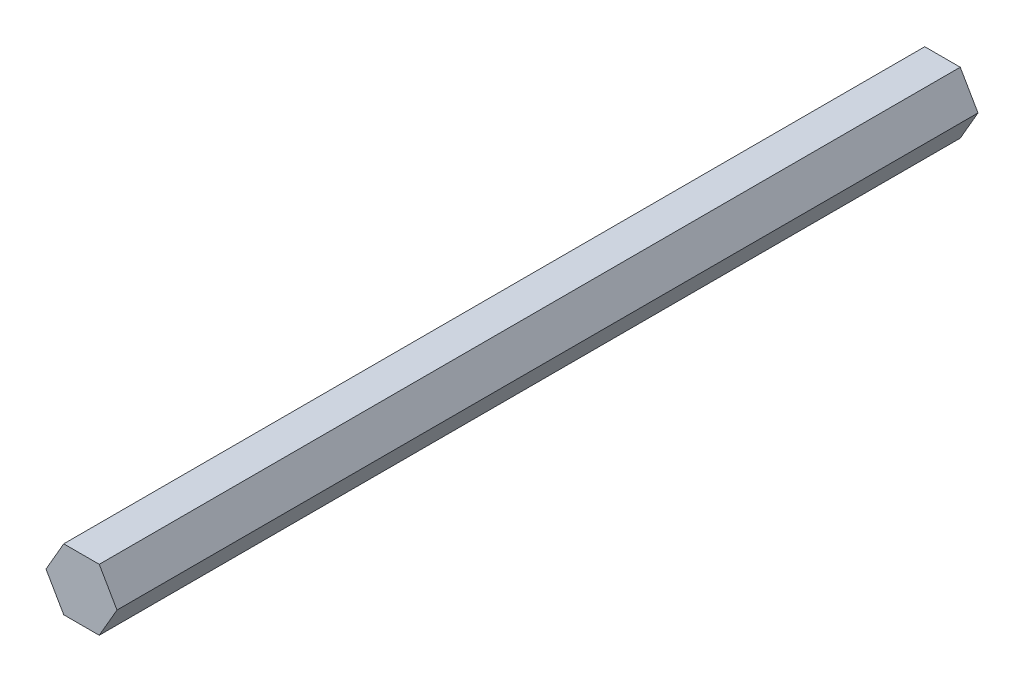
SolidWorks part; units mm, degrees
ref_plane "Front Plane" through (0, 0, 0) normal (0, 0, 1) x (1, 0, 0)
ref_plane "Top Plane" through (0, 0, 0) normal (0, 1, 0) x (1, 0, 0)
ref_plane "Right Plane" through (0, 0, 0) normal (1, 0, 0) x (0, 0, -1)
sketch "Sketch1" plane through (0, 0, 0) normal (0, 0, 1) x (1, 0, 0)
  line L1 (3.6662, 6.35) -> (-3.6662, 6.35)
  line L2 (-3.6662, 6.35) -> (-7.3323, 0)
  line L3 (-7.3323, 0) -> (-3.6662, -6.35)
  line L4 (-3.6662, -6.35) -> (3.6662, -6.35)
  line L5 (3.6662, -6.35) -> (7.3323, 0)
  line L6 (7.3323, 0) -> (3.6662, 6.35)
  circle A0 centre (0, 0) radius 6.35 construction
  dimension "D1" = 12.7
extrude "Boss-Extrude1" add sketch "Sketch1" along normal mid plane 177.8635
ref_axis "Axis1" through (0, 0, -83.82) along (0, 0, 1)
